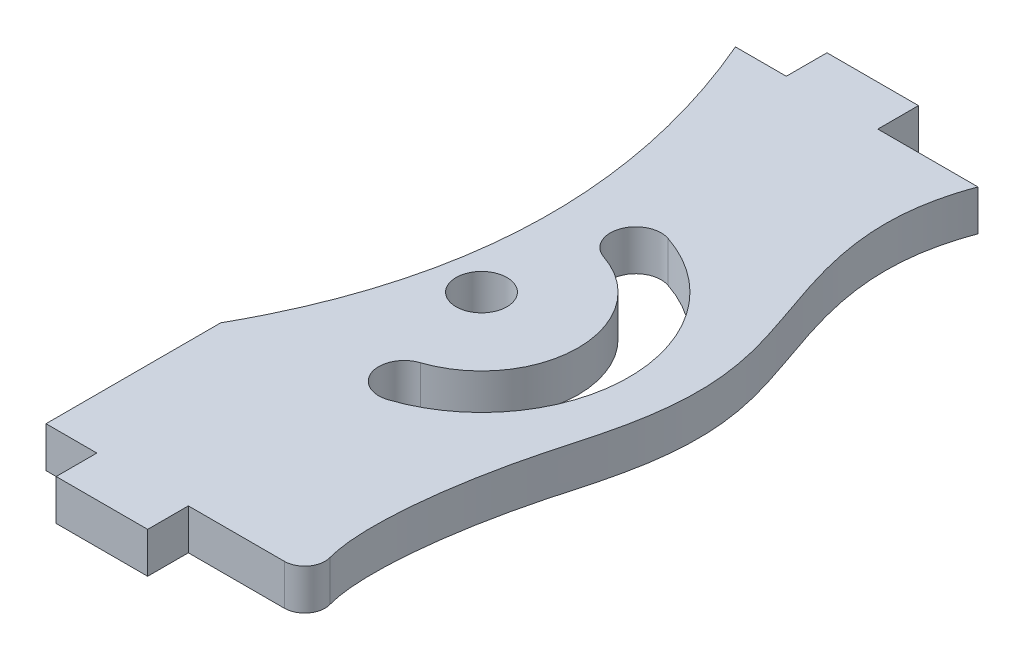
SolidWorks part; units mm, degrees
ref_plane "Alzado" through (0, 0, 0) normal (0, 0, 1) x (1, 0, 0)
ref_plane "Planta" through (0, 0, 0) normal (0, 1, 0) x (1, 0, 0)
ref_plane "Vista lateral" through (0, 0, 0) normal (1, 0, 0) x (0, 0, -1)
sketch "Croquis1" plane through (0, 0, 0) normal (0, 1, 0) x (1, 0, 0)
  line L0 (-30.4594, 18.6892) -> (2.9038, 18.6892) construction
  line L1 (2.715, 0) -> (2.715, 2.0882) construction
  line L3 (-0.3831, 0.651) -> (0.3831, 0.651)
  line L4 (-0.3831, 0.651) -> (-0.3831, -0.651)
  line L5 (-0.3831, -0.651) -> (0.3831, -0.651)
  line L6 (0.3831, 0.651) -> (0.3831, -0.651)
  line L7 (-0.3831, 0.651) -> (0.3831, -0.651) construction
  line L8 (-0.3831, -0.651) -> (0.3831, 0.651) construction
  line L10 (-4.2005, 16.6892) -> (-1.7005, 16.6892)
  line L11 (-1.7005, 16.6892) -> (-1.7005, 18.6892)
  line L12 (-1.7005, 18.6892) -> (2.7995, 18.6892)
  line L13 (2.7995, 18.6892) -> (2.7995, 16.6892)
  line L14 (2.7995, 16.6892) -> (7.7266, 16.6892)
  line L16 (-21.2785, 20.7575) -> (-21.2785, -9.2425) construction
  line L17 (1.8937, -16.3108) -> (6.6151, -16.3108)
  line L18 (1.8937, -18.3108) -> (1.8937, -16.3108)
  line L19 (-2.6063, -18.3108) -> (1.8937, -18.3108)
  line L20 (-2.6063, -16.3108) -> (-2.6063, -18.3108)
  line L21 (-5.1063, -16.3108) -> (-2.6063, -16.3108)
  line L22 (-5.1063, -7.7189) -> (-5.1063, -16.3108)
  circle A0 centre (0, 0) radius 1.25
  arc A3 (4.1833, -4.3012) -> (5.6435, -2.0375) centre (0, 0) ccw
  arc A4 (4.1833, -4.3012) -> (5.6435, -2.0375) centre (0, 0) ccw construction
  arc A10 (6.6151, -16.3108) -> (7.5777, -15.04) centre (6.6151, -15.3108) ccw
  arc A15 (0.6716, -5.9623) -> (6, 0) centre (0, 0) ccw
  arc A17 (1.8924, 5.6937) -> (0.6716, 5.9623) centre (0, 0) ccw
  arc A18 (1.8924, -5.6937) -> (6, 0) centre (0, 0) ccw construction
  arc A19 (2.2867, -6.8799) -> (2.2867, 6.8799) centre (0, 0) ccw
  arc A20 (1.4982, -4.5075) -> (1.4982, 4.5075) centre (0, 0) ccw
  arc A21 (1.4982, -4.5075) -> (2.2867, -6.8799) centre (1.8924, -5.6937) ccw
  arc A22 (2.2867, 6.8799) -> (1.4982, 4.5075) centre (1.8924, 5.6937) ccw
  arc A23 (0.6716, -5.9623) -> (6, 0) centre (0, 0) ccw
  arc A24 (1.8924, 5.6937) -> (0.6716, 5.9623) centre (0, 0) ccw
  spline S0 degree 3 poles (7.5777, -15.04) (7.0091, -13.0184) (7.4797, -8.2818) (9.8371, -0.2699) (9.5069, 5.6257) (5.8998, 11.8316) (7.7266, 16.6892) knots 0.078668 0.078668 0.078668 0.078668 0.337938 0.393993 0.63921 1 1 1 1
  spline S1 degree 2 poles (-4.2005, 16.6892) (1.3277, 3.7559) (-5.1063, -7.7189) knots 0 0 0 1 1 1
  point P12 (6, 0)
  point P13 (5.6435, -1.4969)
  point P14 (5.8147, 1.4795)
  point P15 (4.1833, -4.3012)
  point P16 (-4.7288, 3.8883)
  point P25 (0.3831, 4.7291)
  point P26 (-5.2403, 2.9223)
  point P27 (-5.1063, 3.3548)
  point P28 (0.3831, 5.8206)
  point P29 (0.3831, 5.9878)
  point P32 (-2.6063, 5.4044)
  point P33 (0, 0)
  point P35 (0, 0)
  point P36 (0, 0)
  point P51 (0, 0)
  point P57 (0, 0)
  point P58 (-3.22, 5.069)
  point P59 (1.4249, 5.8299)
  point P60 (4.9745, 3.3548)
  point P61 (0.3831, 5.9906)
  point P62 (-3.22, 5.0628)
  point P63 (0, 0)
  point P64 (-3.22, 5.0628)
  point P65 (0, 0)
  point P66 (-3.22, 5.0628)
  point P67 (0, 0)
  point P68 (1.8937, 5.6937)
  point P69 (0.7407, 5.9541)
  point P70 (-0.3831, 5.9878)
  point P71 (1.424, 5.8206)
  point P72 (4.3329, -4.1504)
  point P73 (6, 0)
  point P74 (0, 0)
  dimension "D1" = 2.5
  dimension "D3" = 1
  dimension "D4" = 30
  dimension "D2" = 12
  dimension "D5" = 2
  dimension "D6" = 4.5
  dimension "D7" = 2.5
  dimension "D8" = 2
  dimension "D9" = 2.5
  dimension "D10" = 4.5
extrude "Saliente-Extruir1" add sketch "Croquis1" along normal blind 2 contours L17 S0 L14 L13 L12 L11 L10 L22 L21 L20 L19 L18 A0 A20 region at (2.0442, 0, 0.6635)
